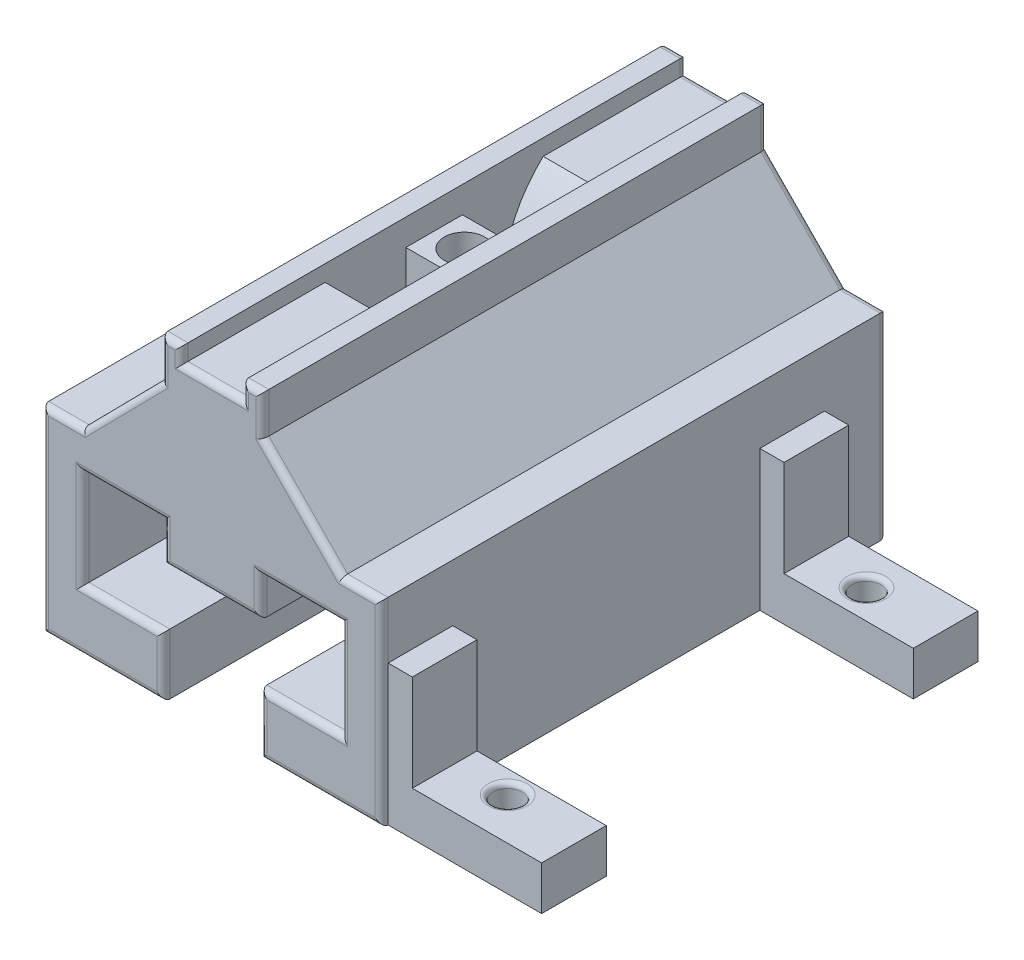
SolidWorks part; units mm, degrees
ref_plane "Front" through (0, 0, 0) normal (0, 0, 1) x (1, 0, 0)
ref_plane "Top" through (0, 0, 0) normal (0, 1, 0) x (1, 0, 0)
ref_plane "Right" through (0, 0, 0) normal (1, 0, 0) x (0, 0, -1)
sketch "Sketch2" plane through (0, 0, 0) normal (0, 0, 1) x (1, 0, 0)
  line L0 (-3.81, 2.6476) -> (-10.16, 2.6476)
  line L1 (-10.16, 2.6476) -> (-10.16, 10.3311)
  line L2 (-10.16, 10.3311) -> (-3.81, 10.3311)
  line L3 (-3.81, 10.3311) -> (-3.81, 7.2831)
  line L4 (-3.81, 7.2831) -> (3.81, 7.2831)
  line L5 (0, -55) -> (0, 55) construction
  line L6 (-3.81, 2.6476) -> (-3.81, -2.1149)
  line L7 (-3.81, -2.1149) -> (-13.335, -2.1149)
  line L8 (-13.335, -2.1149) -> (-13.335, 13.3791)
  line L9 (-13.335, 13.3791) -> (-10.16, 13.3791)
  line L10 (-10.16, 13.3791) -> (-3.9688, 19.6656)
  line L11 (-3.9688, 19.6656) -> (-3.9688, 22.8406)
  line L12 (-3.9688, 22.8406) -> (-2.3813, 22.8406)
  line L13 (-2.3813, 22.8406) -> (-2.3813, 21.5706)
  line L14 (-2.3813, 21.5706) -> (2.3813, 21.5706)
  line L15 (2.3813, 22.8406) -> (2.3813, 21.5706)
  line L16 (3.9688, 22.8406) -> (2.3813, 22.8406)
  line L17 (3.9688, 19.6656) -> (3.9688, 22.8406)
  line L18 (10.16, 13.3791) -> (3.9688, 19.6656)
  line L19 (13.335, 13.3791) -> (10.16, 13.3791)
  line L20 (13.335, -2.1149) -> (13.335, 13.3791)
  line L21 (3.81, -2.1149) -> (13.335, -2.1149)
  line L22 (3.81, 2.6476) -> (3.81, -2.1149)
  line L23 (3.81, 10.3311) -> (3.81, 7.2831)
  line L24 (10.16, 10.3311) -> (3.81, 10.3311)
  line L25 (10.16, 2.6476) -> (10.16, 10.3311)
  line L26 (3.81, 2.6476) -> (10.16, 2.6476)
  point P23 (0, 21.5706)
  point P32 (0, 7.2831)
  dimension "D1" = 4.7625
  dimension "D2" = 9.525
  dimension "D3" = 3.175
  dimension "D4" = 15.494
  dimension "D5" = 3.048
  dimension "D6" = 3.048
  dimension "D7" = 14.2875
  dimension "D8" = 3.175
  dimension "D9" = 1.27
  dimension "D10" = 1.5875
  dimension "D11" = 2.3813
  dimension "D12" = 3.175
  dimension "D13" = 6.35
  dimension "D14" = 3.81
extrude "Boss-Extrude1" add sketch "Sketch2" along normal blind 39.6875
sketch "Sketch3" plane through (0, 21.5706, 0) normal (0, 1, 0) x (1, 0, 0)
  line L0 (0, 0) -> (0, -39.6875) construction
  line L1 (-13.335, -19.8438) -> (13.335, -19.8438) construction
  line L2 (-13.335, -39.6875) -> (-13.335, 0) construction
  line L3 (13.335, -39.6875) -> (13.335, 0) construction
  line L4 (2.3813, 0) -> (-2.3813, 0)
  line L5 (-2.3813, 0) -> (-2.3813, -39.6875)
  line L6 (-2.3813, -39.6875) -> (2.3813, -39.6875)
  line L7 (2.3813, -39.6875) -> (2.3813, 0)
  line L8 (2.3813, 0) -> (-2.3813, 0)
  line L9 (-2.3813, 0) -> (-2.3813, -39.6875)
  line L10 (-2.3813, -39.6875) -> (2.3813, -39.6875)
  line L11 (2.3813, -39.6875) -> (2.3813, 0)
  circle A0 centre (0, -19.8437) radius 1.5875
  dimension "D2" = 3.175
  dimension "D1" = 0
extrude "Cut-Extrude1" cut sketch "Sketch3" against normal blind 39.6875 contours A0 region at (0, 21.5706, 19.8437)
sketch "Sketch4" plane through (0, 7.2831, 0) normal (0, -1, 0) x (1, 0, 0)
  line L1 (0.9165, 18.2562) -> (1.8331, 19.8437)
  line L2 (1.8331, 19.8437) -> (0.9165, 21.4312)
  line L3 (0.9165, 21.4312) -> (-0.9165, 21.4312)
  line L4 (-3.81, 0) -> (3.81, 0)
  line L5 (3.81, 0) -> (3.81, 39.6875)
  line L6 (3.81, 39.6875) -> (-3.81, 39.6875)
  line L7 (-3.81, 39.6875) -> (-3.81, 0)
  line L8 (-3.81, 0) -> (3.81, 0)
  line L9 (3.81, 0) -> (3.81, 39.6875)
  line L10 (3.81, 39.6875) -> (-3.81, 39.6875)
  line L11 (-3.81, 39.6875) -> (-3.81, 0)
  line L12 (-0.9165, 21.4312) -> (-1.8331, 19.8437)
  line L13 (-1.8331, 19.8437) -> (-0.9165, 18.2562)
  line L14 (-0.9165, 18.2562) -> (0.9165, 18.2562)
  circle A0 centre (0, 19.8437) radius 1.5875 construction
  circle M11 centre (0, 19.8437) radius 1.5875
  dimension "D2" = 3.175
  dimension "D1" = 0
extrude "Cut-Extrude3" cut sketch "Sketch4" against normal blind 3.175 contours M11 | L12 L13 M11 | L13 L14 M11 | L14 L1 M11 | L1 L2 M11 | L2 L3 M11 | L3 L12 M11 region at (0.8204, 7.2831, 18.4228) region at (1.6408, 7.2831, 19.8437) region at (0, 7.2831, 19.8437) region at (-0.8204, 7.2831, 18.4228) region at (-1.6408, 7.2831, 19.8437) region at (0.8204, 7.2831, 21.2647) region at (-0.8204, 7.2831, 21.2647)
sketch "Sketch5" plane through (2.3812, 0, 0) normal (-1, 0, 0) x (0, 0, 1)
  line L3 (11.2713, 21.5706) -> (17.6212, 21.5706)
  line L6 (28.4163, 21.5706) -> (22.0663, 21.5706)
  line L7 (28.1707, 7.2831) -> (20.7963, 7.2831)
  line L8 (22.0663, 10.3311) -> (17.6212, 10.3311)
  line L9 (19.8438, 21.5706) -> (19.8438, 7.2831) construction
  line L12 (11.5168, 7.2831) -> (17.6213, 7.2831)
  line L16 (20.7963, 7.2831) -> (17.6213, 7.2831)
  line L19 (22.0663, 20.7705) -> (17.6212, 20.7705)
  line L21 (17.6212, 20.7705) -> (17.6212, 10.3311)
  line L22 (22.0663, 20.7705) -> (22.0663, 10.3311)
  line L24 (17.6212, 21.5706) -> (22.0663, 21.5706)
  arc A0 (28.4163, 21.5706) -> (28.1707, 7.2831) centre (35.1321, 14.3093) ccw
  arc A1 (11.2713, 21.5706) -> (11.5168, 7.2831) centre (4.5554, 14.3093) cw
  dimension "D1" = 4.445
extrude "Cut-Extrude5" cut sketch "Sketch5" along normal up to surface (4.7625 mm away) up to face at (-2.3813, 22.2056, 19.8438)
sketch "Sketch6" plane through (-2.3812, 0, 0) normal (1, 0, 0) x (0, 0, -1)
  line L0 (-26.0766, 10.3311) -> (-13.6109, 10.3311)
  line L1 (-11.5168, 7.2831) -> (-28.1707, 7.2831)
  line L6 (0, 21.5706) -> (0, 22.8406)
  line L7 (0, 22.8406) -> (-39.6875, 22.8406)
  line L8 (-39.6875, 22.8406) -> (-39.6875, 21.5706)
  line L9 (-39.6875, 21.5706) -> (-28.4163, 21.5706)
  line L10 (-28.1707, 7.2831) -> (-11.5168, 7.2831)
  line L11 (-11.2713, 21.5706) -> (0, 21.5706)
  arc A2 (-28.1707, 7.2831) -> (-28.4163, 21.5706) centre (-35.1321, 14.3093) ccw
  arc A3 (-11.2713, 21.5706) -> (-11.5168, 7.2831) centre (-4.5554, 14.3093) ccw
  arc A4 (-28.1707, 7.2831) -> (-26.0766, 10.3311) centre (-35.1321, 14.3093) ccw
  arc A5 (-13.6109, 10.3311) -> (-11.5168, 7.2831) centre (-4.5554, 14.3093) ccw
  dimension "D1" = 0
extrude "Cut-Extrude6" cut sketch "Sketch6" against normal blind 3.175 and the other way blind 8.255 contours L1 A4 L0 A5
fillet "Fillet1" radius 0.508 52 edges at (-6.985, 2.6476, 0) (-10.16, 6.4894, 0) (-6.985, 10.3311, 0) (-3.81, 8.8071, 0) (0, 7.2831, 0) (3.81, 8.8071, 0) (6.985, 10.3311, 0) (10.16, 6.4894, 0) (6.985, 2.6476, 0) (3.81, 0.2664, 0) (8.5725, -2.1149, 0) (13.335, 5.6321, 0) (11.7475, 13.3791, 0) (7.0644, 16.5224, 0) (3.9688, 21.2531, 0) (3.175, 22.8406, 0) (2.3813, 22.2056, 0) (0, 21.5706, 0) (-2.3813, 22.2056, 0) (-3.175, 22.8406, 0) (-3.9688, 21.2531, 0) (-7.0644, 16.5224, 0) (-11.7475, 13.3791, 0) (-13.335, 5.6321, 0) (-8.5725, -2.1149, 0) (-3.81, 0.2664, 0) (-8.5725, -2.1149, 39.6875) (-13.335, 5.6321, 39.6875) (-11.7475, 13.3791, 39.6875) (-7.0644, 16.5224, 39.6875) (-3.9688, 21.2531, 39.6875) (-3.175, 22.8406, 39.6875) (-2.3813, 22.2056, 39.6875) (0, 21.5706, 39.6875) (2.3813, 22.2056, 39.6875) (3.175, 22.8406, 39.6875) (3.9688, 21.2531, 39.6875) (7.0644, 16.5224, 39.6875) (11.7475, 13.3791, 39.6875) (13.335, 5.6321, 39.6875) (8.5725, -2.1149, 39.6875) (3.81, 0.2664, 39.6875) (6.985, 2.6476, 39.6875) (10.16, 6.4894, 39.6875) (6.985, 10.3311, 39.6875) (3.81, 8.8071, 39.6875) (0, 7.2831, 39.6875) (-3.81, 8.8071, 39.6875) (-6.985, 10.3311, 39.6875) (-10.16, 6.4894, 39.6875) (-6.985, 2.6476, 39.6875) (-3.81, 0.2664, 39.6875)
sketch "Sketch7" plane through (13.335, 0, 0) normal (1, 0, 0) x (0, 0, -1)
  line L0 (-39.1795, -2.1149) -> (-0.508, -2.1149) construction
  line L1 (-39.1795, -2.1149) -> (-34.0995, -2.1149)
  line L2 (-39.1795, -2.1149) -> (-39.1795, 8.9054)
  line L3 (-39.1795, 8.9054) -> (-34.0995, 8.9054)
  line L4 (-34.0995, -2.1149) -> (-34.0995, 8.9054)
  line L5 (-9.9695, -2.1149) -> (-4.8895, -2.1149)
  line L6 (-9.9695, -2.1149) -> (-9.9695, 8.9054)
  line L7 (-9.9695, 8.9054) -> (-4.8895, 8.9054)
  line L8 (-4.8895, -2.1149) -> (-4.8895, 8.9054)
  point P11 (-7.4295, 8.9054)
  dimension "D1" = 5.08
  dimension "D2" = 24.13
extrude "Boss-Extrude2" add sketch "Sketch7" along normal blind 1.905
sketch "Sketch8" plane through (15.24, 0, 0) normal (1, 0, 0) x (0, 0, -1)
  line L0 (-39.1795, 1.336) -> (-34.0995, 1.336)
  line L1 (-9.9695, 1.336) -> (-4.8895, 1.336)
  line L4 (-39.1795, 8.9054) -> (-39.1795, -2.1149)
  line L5 (-39.1795, -2.1149) -> (-34.0995, -2.1149)
  line L6 (-34.0995, -2.1149) -> (-34.0995, 8.9054)
  line L7 (-34.0995, 8.9054) -> (-39.1795, 8.9054)
  line L8 (-39.1795, 8.9054) -> (-39.1795, -2.1149)
  line L9 (-39.1795, -2.1149) -> (-34.0995, -2.1149)
  line L10 (-34.0995, -2.1149) -> (-34.0995, 8.9054)
  line L11 (-34.0995, 8.9054) -> (-39.1795, 8.9054)
  line L12 (-9.9695, 8.9054) -> (-9.9695, -2.1149)
  line L13 (-9.9695, -2.1149) -> (-4.8895, -2.1149)
  line L14 (-4.8895, -2.1149) -> (-4.8895, 8.9054)
  line L15 (-4.8895, 8.9054) -> (-9.9695, 8.9054)
  line L16 (-9.9695, 8.9054) -> (-9.9695, -2.1149)
  line L17 (-9.9695, -2.1149) -> (-4.8895, -2.1149)
  line L18 (-4.8895, -2.1149) -> (-4.8895, 8.9054)
  line L19 (-4.8895, 8.9054) -> (-9.9695, 8.9054)
  line M9 (-39.1795, 8.9054) -> (-39.1795, -2.1149)
  line M10 (-39.1795, -2.1149) -> (-34.0995, -2.1149)
  line M11 (-34.0995, -2.1149) -> (-34.0995, 8.9054)
  dimension "D1" = 0
  dimension "D2" = 0
extrude "Boss-Extrude3" add sketch "Sketch8" along normal blind 10.16 contours L0 M9 M10 M11 | L17 L18 L1 L16 region at (15.24, -0.3894, 36.6395) region at (15.24, -0.3894, 7.4295)
sketch "Sketch9" plane through (0, -2.1149, 0) normal (0, -1, 0) x (1, 0, 0)
  line L11 (3.81, 39.1795) -> (3.81, 0.508)
  line L12 (3.81, 0.508) -> (13.335, 0.508)
  line L13 (13.335, 0.508) -> (13.335, 4.8895)
  line L14 (13.335, 4.8895) -> (25.4, 4.8895)
  line L15 (25.4, 4.8895) -> (25.4, 9.9695)
  line L16 (25.4, 9.9695) -> (13.335, 9.9695)
  line L17 (13.335, 9.9695) -> (13.335, 34.0995)
  line L18 (13.335, 34.0995) -> (25.4, 34.0995)
  line L19 (25.4, 34.0995) -> (25.4, 39.1795)
  line L20 (25.4, 39.1795) -> (13.335, 39.1795)
  line L21 (13.335, 39.1795) -> (3.81, 39.1795)
  line L22 (3.81, 39.1795) -> (3.81, 0.508)
  line L23 (3.81, 0.508) -> (13.335, 0.508)
  line L24 (13.335, 0.508) -> (13.335, 4.8895)
  line L25 (13.335, 4.8895) -> (25.4, 4.8895)
  line L26 (25.4, 4.8895) -> (25.4, 9.9695)
  line L27 (25.4, 9.9695) -> (13.335, 9.9695)
  line L28 (13.335, 9.9695) -> (13.335, 34.0995)
  line L29 (13.335, 34.0995) -> (25.4, 34.0995)
  line L30 (25.4, 34.0995) -> (25.4, 39.1795)
  line L31 (25.4, 39.1795) -> (13.335, 39.1795)
  line L32 (13.335, 39.1795) -> (3.81, 39.1795)
  circle A0 centre (19.431, 7.6835) radius 1.143
  circle A1 centre (19.431, 35.8775) radius 1.143
  dimension "D2" = 2.286
  dimension "D4" = 2.286
  dimension "D6" = 6.096
  dimension "D7" = 6.096
  dimension "D3" = 2.286
  dimension "D5" = 1.778
  dimension "D1" = 0
extrude "Cut-Extrude7" cut sketch "Sketch9" against normal up to next contours A1 | A0 region at (19.431, -2.1149, 7.6835) region at (19.431, -2.1149, 35.8775)
fillet "Fillet2" radius 0.381 4 edges at (20.574, -2.1149, 7.6835) (20.574, -2.1149, 35.8775) (18.288, 1.336, 7.6835) (18.288, 1.336, 35.8775)
